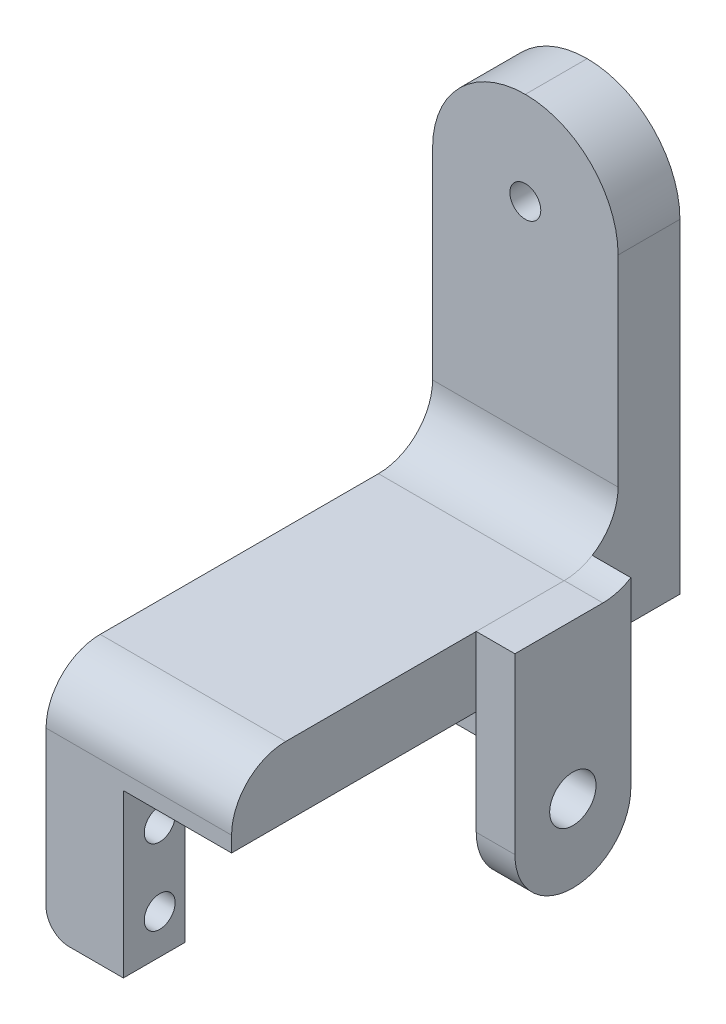
SolidWorks part; units mm, degrees
ref_plane "Front Plane" through (0, 0, 0) normal (0, 0, 1) x (1, 0, 0)
ref_plane "Top Plane" through (0, 0, 0) normal (0, 1, 0) x (1, 0, 0)
ref_plane "Right Plane" through (0, 0, 0) normal (1, 0, 0) x (0, 0, -1)
sketch "Sketch2" plane through (0, -0.0002, -27.9978) normal (0, 0, -1) x (1, 0, 0)
  line L1 (45.1952, -27.127) -> (69.1952, -27.127)
  line L2 (45.1952, -27.127) -> (45.1952, 47.873)
  line L3 (45.1952, 47.873) -> (69.1952, 47.873)
  line L4 (69.1952, -27.127) -> (69.1952, 47.873)
  dimension "D4" = 75
extrude "Boss-Extrude1" add sketch "Sketch2" along normal blind 8
fillet "Fillet1" radius 12 2 edges at (45.1952, 27.1268, -31.9981) (69.1952, 27.1268, -31.9981)
sketch "Sketch3" plane through (0, -0.0002, -27.9978) normal (0, 0, 1) x (1, 0, 0)
  line L0 (69.1952, 15.127) -> (69.1952, -47.873) construction
  line L1 (45.1952, -47.873) -> (69.1952, -47.873)
  line L2 (45.1952, -47.873) -> (45.1952, -17.873)
  line L3 (45.1952, -17.873) -> (69.1952, -17.873)
  line L4 (69.1952, -47.873) -> (69.1952, -17.873)
  dimension "D1" = 30
extrude "Boss-Extrude2" add sketch "Sketch3" along normal blind 50
sketch "Sketch4" plane through (69.1952, 0, 0) normal (1, 0, 0) x (0, 0, -1)
  line L2 (27.9977, -54.1007) -> (27.9977, -26.8732)
  line L3 (27.9977, -26.8732) -> (-14.0023, -26.8732)
  line L4 (-14.0023, -54.1007) -> (-14.0023, -26.8732)
  line L5 (-22.0023, -17.8728) -> (35.9977, -17.8728) construction
  line L6 (35.998, 15.1267) -> (35.9975, -47.8733) construction
  line L7 (6.9977, -17.8728) -> (6.9977, -54.1007) construction
  line L8 (27.9977, -54.1007) -> (-14.0023, -54.1007)
  dimension "D1" = 21
  dimension "D2" = 42
extrude "Cut-Extrude1" cut sketch "Sketch4" against normal up to surface (24 mm away) up to face at (45.1952, -16.8731, -13.9977)
fillet "Fillet2" radius 7 2 edges at (57.1952, -17.8728, 22.0023) (57.1952, -17.8732, -27.9977)
sketch "Sketch5" plane through (69.1952, 0, 0) normal (1, 0, 0) x (0, 0, -1)
  line L10 (-22.0025, -47.8728) -> (-22.0024, -24.8728) construction
  line L11 (35.998, 15.1267) -> (35.9975, -47.8733) construction
  line L20 (20.9977, -17.8732) -> (-15.0023, -17.8729)
  line L21 (-22.0024, -24.8728) -> (-22.0025, -47.8728)
  line L22 (-22.0025, -47.8728) -> (-14.0023, -47.8729)
  line L23 (-14.0023, -47.8729) -> (-14.0023, -26.8732)
  line L24 (-14.0023, -26.8732) -> (27.9977, -26.8732)
  line L25 (27.9977, -26.8732) -> (27.9977, -47.8732)
  line L26 (27.9977, -47.8732) -> (35.9975, -47.8733)
  line L27 (35.9975, -47.8733) -> (35.998, 15.1267)
  line L28 (35.998, 15.1267) -> (27.998, 15.1268)
  line L29 (27.998, 15.1268) -> (27.9978, -10.8732)
  line L31 (-22.0024, -26.8732) -> (-22.0025, -47.8728)
  line L32 (-22.0025, -47.8728) -> (35.9975, -47.8733)
  line L34 (-22.0024, -26.8732) -> (35.9976, -26.8732)
  line L37 (35.9975, -47.8733) -> (35.9976, -26.8732)
  arc A2 (-15.0023, -17.8729) -> (-22.0024, -24.8728) centre (-15.0024, -24.8729) ccw
  arc A3 (20.9977, -17.8732) -> (27.9978, -10.8732) centre (20.9978, -10.8732) ccw
  dimension "D1" = 0
extrude "Cut-Extrude3" cut sketch "Sketch5" against normal blind 14
sketch "Sketch6" plane through (69.1952, 0, 0) normal (1, 0, 0) x (0, 0, -1)
  line L0 (6.9976, -26.8732) -> (6.9976, -51.8245) construction
  line L1 (35.9976, -26.8732) -> (-22.0024, -26.8732) construction
  line L2 (1.5238, -51.8245) -> (14.5238, -51.8245) construction
  line L3 (-15.0023, -17.8729) -> (20.9977, -17.8732) construction
  line L4 (21.0341, -17.8731) -> (9.6476, -17.8731)
  line L5 (24.6476, -16.8463) -> (24.6476, -47.8732)
  line L6 (24.6476, -47.8732) -> (9.6476, -47.8731)
  line L7 (9.6476, -17.8731) -> (9.6476, -47.8731)
  line L8 (-13.0023, -47.8732) -> (26.9977, -47.8732) construction
  circle A0 centre (-3.1523, -37.8732) radius 3 construction
  circle A1 centre (17.1476, -37.8732) radius 3
  arc A2 (20.9977, -17.8732) -> (27.9978, -10.8732) centre (20.9978, -10.8732) ccw construction
  arc A3 (21.0341, -17.8731) -> (24.6476, -16.8463) centre (20.9978, -10.8732) ccw
  dimension "D4" = 30
extrude "Boss-Extrude3" add sketch "Sketch6" along normal blind 5
fillet "Fillet3" radius 3 2 edges at (45.1952, -47.8728, 18.0024) (45.1952, -47.8732, -31.9976)
sketch "Sketch7" plane through (0, -0.0002, -27.9978) normal (0, 0, 1) x (1, 0, 0)
  line L0 (57.1952, 27.127) -> (57.1952, 15.127) construction
  arc A0 (69.1952, 15.127) -> (57.1952, 27.127) centre (57.1952, 15.127) ccw construction
  arc A1 (69.1952, 15.127) -> (57.1952, 27.127) centre (57.1952, 15.127) ccw construction
  circle A2 centre (57.1952, 15.127) radius 2
extrude "Cut-Extrude4" cut sketch "Sketch7" against normal through all
sketch "Sketch8" plane through (0, -0.0003, -35.9978) normal (0, 0, -1) x (-1, 0, 0)
  circle A0 centre (-57.1952, 15.127) radius 3
extrude "Cut-Extrude5" cut sketch "Sketch8" against normal blind 4
sketch "Sketch9" plane through (55.1952, 0, 0) normal (1, 0, 0) x (0, 0, -1)
  circle A0 centre (31.2977, -42.7732) radius 2
  circle A1 centre (31.2977, -32.9732) radius 2
  circle A2 centre (-17.3023, -42.7732) radius 2
  circle A3 centre (-17.3023, -32.9732) radius 2
extrude "Cut-Extrude6" cut sketch "Sketch9" against normal blind 10
fillet "Fillet4" radius 7.5 2 edges at (71.6952, -47.8732, -24.6476) (71.6952, -47.8731, -9.6476)
